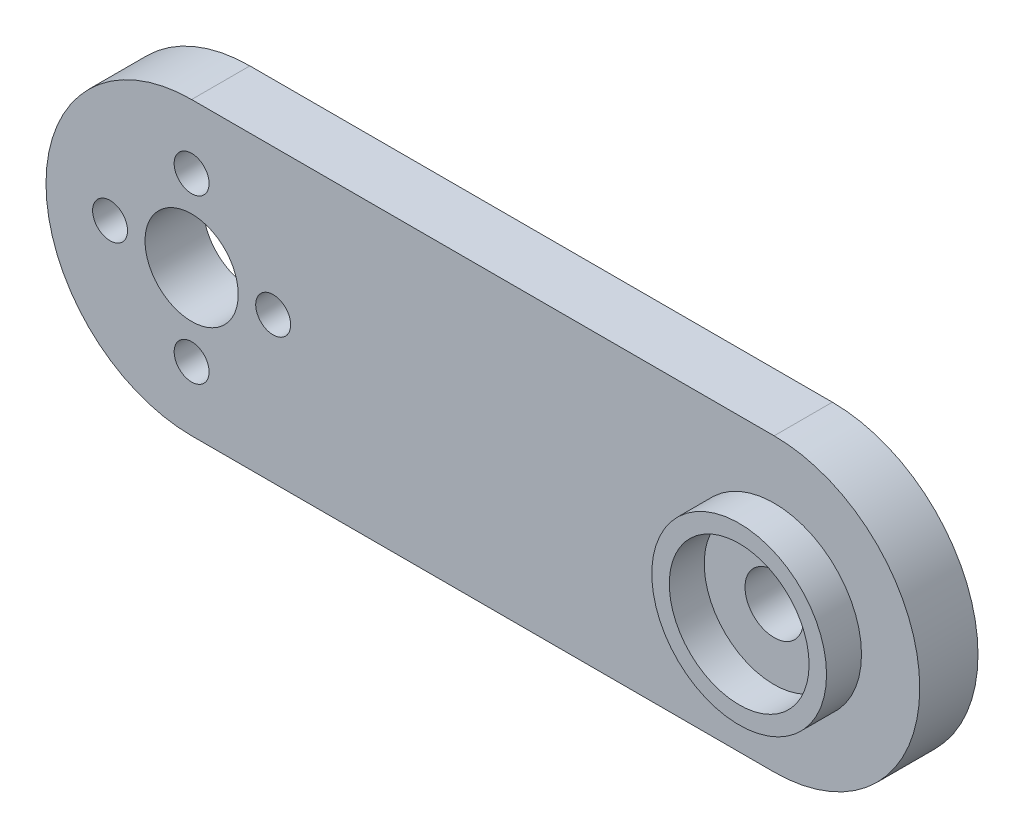
SolidWorks part; units mm, degrees
ref_plane "Front Plane" through (0, 0, 0) normal (0, 0, 1) x (1, 0, 0)
ref_plane "Top Plane" through (0, 0, 0) normal (0, 1, 0) x (1, 0, 0)
ref_plane "Right Plane" through (0, 0, 0) normal (1, 0, 0) x (0, 0, -1)
sketch "Sketch1" plane through (0, 0, 0) normal (0, 0, 1) x (1, 0, 0)
  line L1 (0, 0) -> (50, 0)
  line L2 (0, 0) -> (0, 25)
  line L3 (0, 25) -> (50, 25)
  line L4 (50, 0) -> (50, 25)
  line L5 (50, 15) -> (50, 10)
  circle A0 centre (0, 12.5) radius 12.5
  circle A4 centre (50, 12.5) radius 12.5
  dimension "D1" = 25
  dimension "D4" = 50
extrude "Boss-Extrude2" add sketch "Sketch1" along normal blind 5 contours L2 L1 L4 L3 | A0 | A4
sketch "Sketch3" plane through (0, 0, 5) normal (0, 0, 1) x (1, 0, 0)
  line L0 (0, 0) -> (50, 0) construction
  line L1 (0, 25) -> (50, 25) construction
  line L2 (0, 0) -> (50, 0) construction
  line L3 (0, 25) -> (50, 25) construction
  line L4 (0, 5.5) -> (0, 19.5)
  line L5 (-7, 12.5) -> (7, 12.5)
  arc A0 (50, 0) -> (50, 25) centre (50, 12.5) ccw construction
  arc A1 (0, 25) -> (0, 0) centre (0, 12.5) ccw construction
  arc A2 (50, 0) -> (50, 25) centre (50, 12.5) ccw construction
  arc A3 (0, 25) -> (0, 0) centre (0, 12.5) ccw construction
  circle A4 centre (0, 12.5) radius 4
  circle A5 centre (50, 12.5) radius 2.5
  circle A8 centre (50, 12.5) radius 6
  circle A9 centre (50, 12.5) radius 7.5
  circle A10 centre (0, 19.5) radius 1.5
  circle A11 centre (0, 5.5) radius 1.5
  circle A12 centre (-7, 12.5) radius 1.5
  circle A13 centre (7, 12.5) radius 1.5
  point P14 (0, 12.5)
  point P18 (0, 12.5)
  dimension "D1" = 5
  dimension "D2" = 8
  dimension "D3" = 14
  dimension "D4" = 3
  dimension "D5" = 12
  dimension "D6" = 15
  dimension "D7" = 3
  dimension "D9" = 3
  dimension "D10" = 3
  dimension "D8" = 14
extrude "Cut-Extrude3" cut sketch "Sketch3" against normal up to next contours A4 | A5
extrude "Boss-Extrude3" add sketch "Sketch3<3>" along normal blind 3 contours A9 A8 region at (42.7121, 12.5, 5)
sketch "Sketch3<3>" plane through (0, 0, 5) normal (0, 0, 1) x (1, 0, 0) same geometry as "Sketch3"
extrude "Cut-Extrude4" cut sketch "Sketch3<4>" against normal up to next contours A12 | A10 | A13 | A11 region at (-8.4576, 12.5, 5) region at (-1.0307, 20.5307, 5) region at (7, 13.9576, 5) region at (1.0307, 6.5307, 5)
sketch "Sketch3<4>" plane through (0, 0, 5) normal (0, 0, 1) x (1, 0, 0) same geometry as "Sketch3"
equation "\"LinkCrank_Length\"=50"
equation "\"D4@Sketch1\"=\"LinkCrank_Length\""
